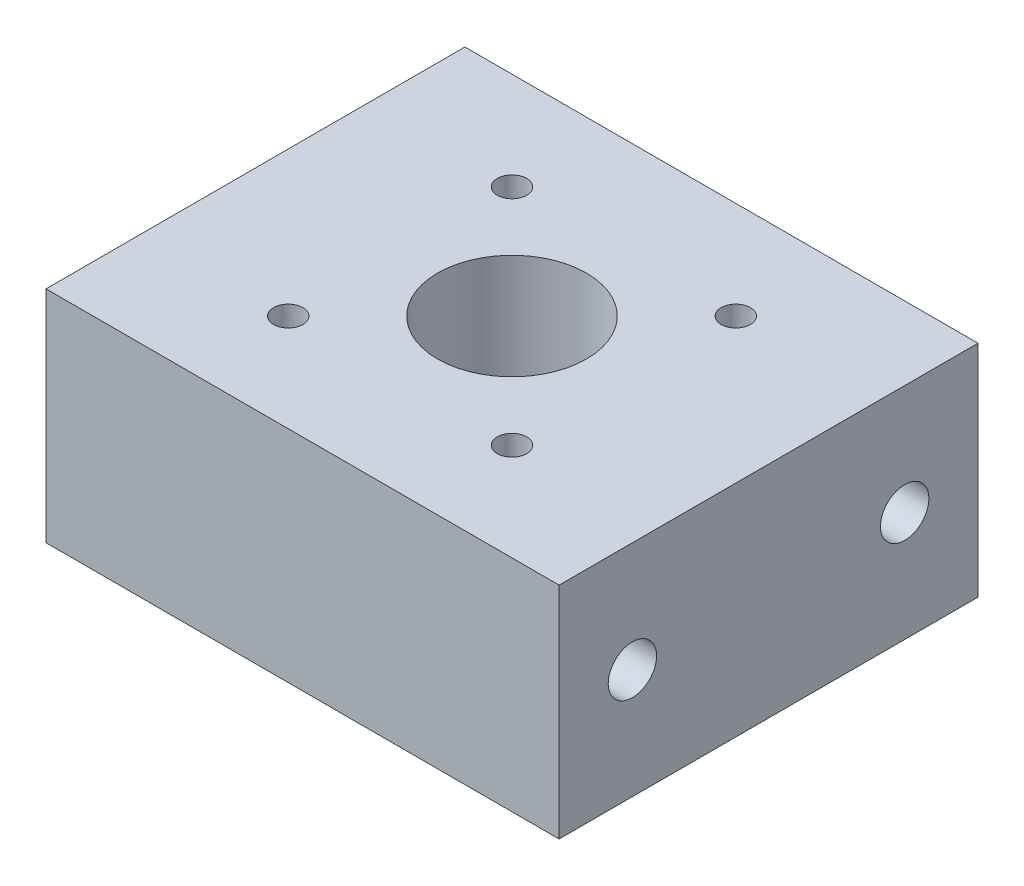
SolidWorks part; units mm, degrees
ref_plane "Front Plane" through (0, 0, 0) normal (0, 0, 1) x (1, 0, 0)
ref_plane "Top Plane" through (0, 0, 0) normal (0, 1, 0) x (1, 0, 0)
ref_plane "Right Plane" through (0, 0, 0) normal (1, 0, 0) x (0, 0, -1)
sketch "Sketch1" plane through (0, 0, 0) normal (0, 1, 0) x (1, 0, 0)
  line L1 (-17.5, -14.2875) -> (17.5, -14.2875)
  line L2 (-17.5, -14.2875) -> (-17.5, 14.2875)
  line L3 (-17.5, 14.2875) -> (17.5, 14.2875)
  line L4 (17.5, -14.2875) -> (17.5, 14.2875)
  line L5 (-17.5, -14.2875) -> (17.5, 14.2875) construction
  line L6 (-17.5, 14.2875) -> (17.5, -14.2875) construction
  point P0 (0, 0)
  dimension "D1" = 35
  dimension "D2" = 28.575
extrude "Boss-Extrude1" add sketch "Sketch1" against normal blind 15
sketch "Sketch2" plane through (0, 0, 0) normal (0, 1, 0) x (1, 0, 0)
  circle A0 centre (0, 0) radius 5.08
  dimension "D2" = 10.16
extrude "Cut-Extrude2" cut sketch "Sketch2" against normal blind 30
sketch "Sketch4" plane through (0, 0, 0) normal (0, 1, 0) x (1, 0, 0)
  line L0 (7.633, 7.633) -> (7.633, 0) construction
  line L1 (7.633, 0) -> (0, 0) construction
  line L2 (0, 0) -> (-7.633, 0) construction
  line L3 (-7.633, 0) -> (-7.633, 7.633) construction
  line L4 (7.633, 0) -> (7.633, -7.633) construction
  line L5 (-7.633, 0) -> (-7.633, -7.633) construction
  circle A0 centre (7.633, 7.633) radius 1
  circle A1 centre (-7.633, 7.633) radius 1
  circle A2 centre (-7.633, -7.633) radius 1
  circle A3 centre (7.633, -7.633) radius 1
  dimension "D2" = 2
  dimension "D1" = 7.633
extrude "Cut-Extrude3" cut sketch "Sketch4" against normal blind 15
hole_wizard "M4x0.7 Tapped Hole1" positions "Sketch6" profile "Sketch5" tap size "M4x0.7" standard "ANSI Metric" end condition through all
sketch "Sketch6" plane through (-17.5, 0, 0) normal (1, 0, 0) x (0, -1, 0)
  line L1 (7.5, 14.2875) -> (7.5, -14.2875) construction
  line L2 (15, 14.2875) -> (0, 14.2875) construction
  line L3 (15, -14.2875) -> (0, -14.2875) construction
  point P0 (7.5, 9.2875)
  point P2 (7.5, -9.2875)
  dimension "D1" = 5
  dimension "D2" = 5
sketch "Sketch5" plane through (-17.5, -7.5, -9.2875) normal (0, 1, 0) x (0, 0, 1)
  line L0 (0, 0) -> (0, 35)
  line L1 (0, 35) -> (1.65, 35)
  line L2 (1.65, 35) -> (1.65, 0)
  line L5 (1.65, 0) -> (0, 0)
  line L11 (0, -6.35) -> (0, 107.95) construction
  dimension "Thru Tap Drill Dia." = 3.3
  dimension "Thru Tap Drill Depth" = 35
cosmetic thread "Hole Thread1" parameters "D2"=4
cosmetic thread "Hole Thread2" parameters "D2"=4
fillet "Fillet1" [suppressed] type full round
fillet "Fillet2" [suppressed] type full round
sketch "Sketch19" [suppressed] plane through (0, -15, 0) normal (0, -1, 0) x (1, 0, 0)
  line L0 (-17.5, -16.25) -> (17.5, -16.25) construction
  line L1 (17.5, 16.25) -> (11, 16.25)
  line L2 (17.5, 16.25) -> (17.5, -16.25)
  line L3 (17.5, -16.25) -> (11, -16.25)
  line L4 (11, 16.25) -> (11, -16.25)
  line L5 (14.25, -16.25) -> (14.25, 16.25) construction
  line L6 (17.5, 0) -> (11, 0) construction
  point P152 (14.25, 0)
  dimension "D1" = 11
extrude "Cut-Extrude13" [suppressed] cut sketch "Sketch19" against normal through all
sketch "Sketch20" [suppressed] plane through (-17.5, 0, 0) normal (-1, 0, 0) x (0, 0, 1)
  line L1 (-1.5216, -9.5) -> (1.5216, -9.5)
  line L2 (-1.5216, -9.5) -> (-1.5216, -5.5)
  line L3 (-1.5216, -5.5) -> (1.5216, -5.5)
  line L4 (1.5216, -9.5) -> (1.5216, -5.5)
  line L5 (0, -5.5) -> (0, -9.5) construction
  line L6 (-1.5216, -7.5) -> (1.5216, -7.5) construction
  circle A0 centre (-8.75, -7.5) radius 7.5
  circle A1 centre (8.75, -7.5) radius 7.5
  arc A3 (-8.75, 0) -> (-8.75, -15) centre (-8.75, -7.5) ccw construction
  point P100 (0, -7.5)
  circle M5 centre (-11.25, -7.5) radius 1.65
  circle M6 centre (11.25, -7.5) radius 1.65
  line M7 (-8.75, -15) -> (8.75, -15)
  arc M8 (8.75, -15) -> (8.75, 0) centre (8.75, -7.5) ccw
  line M9 (8.75, 0) -> (-8.75, 0)
  arc M10 (-8.75, 0) -> (-8.75, -15) centre (-8.75, -7.5) ccw
  dimension "D1" = 4
extrude "Cut-Extrude14" [suppressed] cut sketch "Sketch20" against normal blind 7 flip side to cut contours L2 A0 M9 M10 M7 M5 | A1 L3 A0 L1 | L2 A0 | L4 A1 | A1 L4 M8 M6
